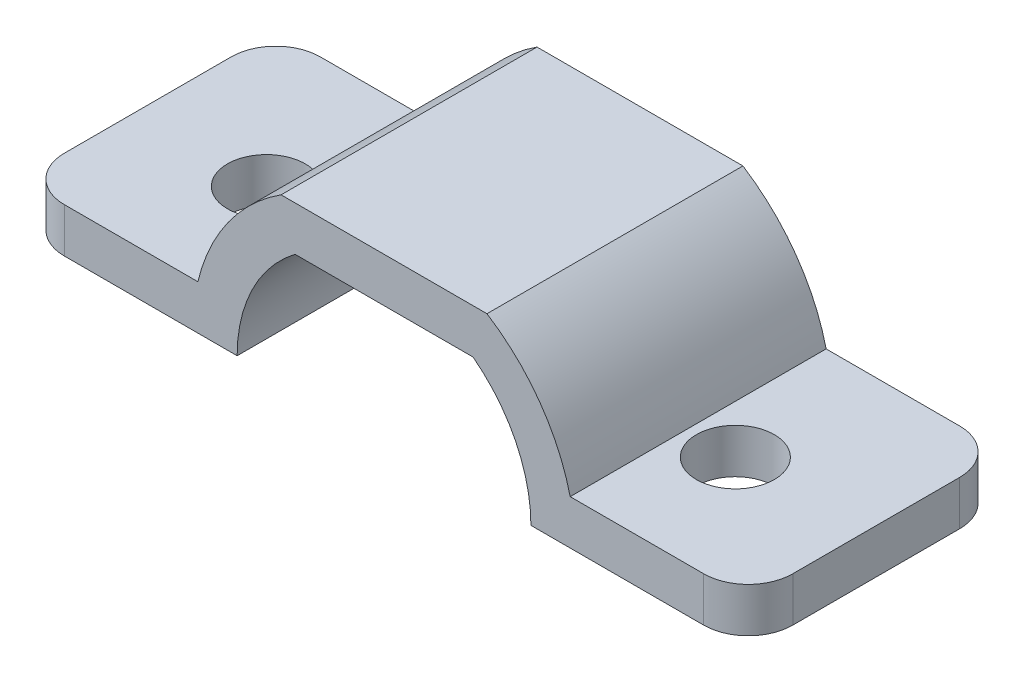
SolidWorks part; units mm, degrees
ref_plane "Front Plane" through (0, 0, 0) normal (0, 0, 1) x (1, 0, 0)
ref_plane "Top Plane" through (0, 0, 0) normal (0, 1, 0) x (1, 0, 0)
ref_plane "Right Plane" through (0, 0, 0) normal (1, 0, 0) x (0, 0, -1)
sketch "Sketch2" plane through (0, 0, 0) normal (0, 0, 1) x (1, 0, 0)
  line L0 (6.3377, 0) -> (-6.3377, 0) construction
  line L4 (-6.6, 0) -> (6.6, 0)
  line L6 (-3.9997, 5.25) -> (3.9997, 5.25)
  line L8 (-4.6257, 7.25) -> (4.6257, 7.25)
  line L9 (-8.3642, -2) -> (8.3642, -2) construction
  line L10 (0, 0) -> (0, 13.1029) construction
  line L11 (8.6, 0) -> (16.3642, 0)
  line L13 (8.3642, 2) -> (16.3642, 2)
  line L14 (16.3642, 0) -> (16.3642, 2)
  line L15 (-8.3642, 2) -> (-16.3642, 2)
  line L16 (-16.3642, 0) -> (-16.3642, 2)
  line L17 (-8.6, 0) -> (-16.3642, 0)
  line L19 (8.6, 0) -> (6.6, 0)
  line L20 (-6.6, 0) -> (-8.6, 0)
  arc A2 (6.6, 0) -> (3.9997, 5.25) centre (0, 0) ccw
  arc A3 (-3.9997, 5.25) -> (-6.6, 0) centre (0, 0) ccw
  arc A4 (-4.6257, 7.25) -> (-8.6, 0) centre (0, 0) ccw
  arc A5 (8.6, 0) -> (4.6257, 7.25) centre (0, 0) ccw
  arc A6 (8.3642, -2) -> (4.6257, 7.25) centre (0, 0) ccw construction
  arc A7 (-4.6257, 7.25) -> (-8.3642, -2) centre (0, 0) ccw construction
  point P6 (0, 0)
  dimension "D1" = 5.25
  dimension "D2" = 6.6
  dimension "D4" = 2
  dimension "D5" = 8
  dimension "D3" = 2
extrude "Boss-Extrude1" add sketch "Sketch2" along normal mid plane 11.5 contours A5 L11 L14 L13 | A4 L15 L16 L17 region at (-12.4427, 1.005, 0) region at (12.4427, 1.005, 0)
extrude "Boss-Extrude2" add sketch "Sketch2<4>" along normal mid plane 11.5 contours L19 A5 L8 A4 L20 A3 L6 A2 region at (-7.6, 0.1867, 0)
sketch "Sketch2<4>" plane through (0, 0, 0) normal (0, 0, 1) x (1, 0, 0) same geometry as "Sketch2"
sketch "Sketch3" plane through (0, 2, 0) normal (0, 1, 0) x (1, 0, 0)
  line L0 (0, 0) -> (0, 6.8294) construction
  line L2 (-8.3642, 5.75) -> (-16.3642, 5.75) construction
  circle A0 centre (-10.535, -0.5) radius 1.75
  dimension "D1" = 3.5
  dimension "D2" = 10.535
  dimension "D4" = 6.25
extrude "Cut-Extrude2" cut sketch "Sketch3" against normal through all
mirror "Mirror1" about plane through (0, 0, 0) normal (1, 0, 0) of "Cut-Extrude2"
fillet "Fillet1" radius 2 4 edges at (-16.3642, 1, 5.75) (-16.3642, 1, -5.75) (16.3642, 1, -5.75) (16.3642, 1, 5.75)
